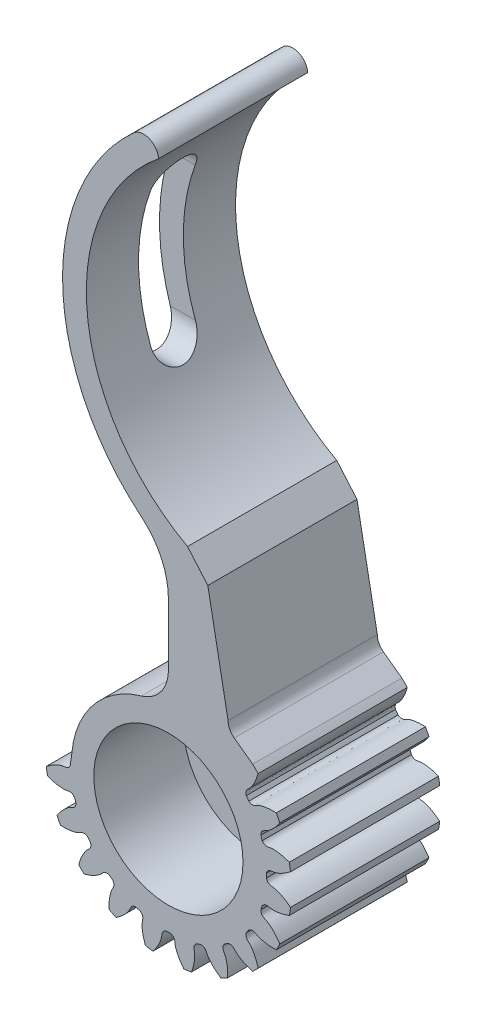
SolidWorks part; units mm, degrees
material "聚脂树脂"
ref_plane "前视基准面" through (0, 0, 0) normal (0, 0, 1) x (1, 0, 0)
ref_plane "上视基准面" through (0, 0, 0) normal (0, 1, 0) x (1, 0, 0)
ref_plane "右视基准面" through (0, 0, 0) normal (1, 0, 0) x (0, 0, -1)
other "Configuration Table"
sketch "草图1" plane through (0, 0, 0) normal (0, 0, 1) x (1, 0, 0)
  circle A0 centre (0, 0) radius 16.5
extrude "凸台-拉伸1" add sketch "草图1" along normal blind 20
ref_axis "基准轴1" through (0, 0, -1.5) along (0, 0, 1)
sketch "草图2" plane through (0, 0, 0) normal (0, 0, 1) x (1, 0, 0)
  line L0 (0, 0) -> (0, 16.5) construction
  circle A0 centre (0, 0) radius 16.5 construction
  arc A1 (0.29, 13.1218) -> (-0.29, 13.1218) centre (0, 0) ccw
  arc A2 (4.7717, 18.7474) -> (-4.7717, 18.7474) centre (0, 0) ccw
  spline S0 degree 3 poles (0.29, 13.1218) (0.9168, 13.3402) (0.8356, 13.7807) (0.9193, 14.205) (0.9283, 14.2463) (0.9395, 14.293) (0.9529, 14.3448) (0.969, 14.4018) (0.9878, 14.4638) (1.0095, 14.5309) (1.0345, 14.6028) (1.0629, 14.6795) (1.0948, 14.7608) (1.1305, 14.8467) (1.1702, 14.9371) (1.2141, 15.0317) (1.2623, 15.1305) (1.315, 15.2334) (1.3725, 15.3401) (1.4349, 15.4506) (1.5023, 15.5646) (1.575, 15.6821) (1.653, 15.8029) (1.7366, 15.9267) (1.826, 16.0534) (1.9211, 16.1829) (2.0223, 16.3149) (2.1296, 16.4493) (2.2432, 16.5859) (2.3632, 16.7244) (2.4897, 16.8646) (2.6229, 17.0065) (2.7628, 17.1496) (2.9095, 17.2939) (3.0632, 17.4391) (3.224, 17.585) (3.3918, 17.7313) (3.567, 17.8779) (3.7493, 18.0245) (3.9391, 18.1709) (4.1363, 18.3167) (4.4122, 18.5125) (4.6259, 18.6545) (4.7717, 18.7474) knots 0 0 0 0 0.165916 0.170906 0.176664 0.183189 0.190482 0.198542 0.207371 0.216967 0.22733 0.238462 0.250361 0.263027 0.276462 0.290664 0.305634 0.321371 0.337876 0.355149 0.37319 0.391998 0.411574 0.431917 0.453028 0.474907 0.497554 0.520968 0.54515 0.570099 0.595817 0.622302 0.649554 0.677575 0.706363 0.735918 0.766242 0.797333 0.829191 0.861818 0.895212 0.929373 1 1 1 1
  spline S1 degree 3 poles (-0.29, 13.1218) (-0.9168, 13.3402) (-0.8356, 13.7807) (-0.9193, 14.205) (-0.9283, 14.2463) (-0.9395, 14.293) (-0.9529, 14.3448) (-0.969, 14.4018) (-0.9878, 14.4638) (-1.0095, 14.5309) (-1.0345, 14.6028) (-1.0629, 14.6795) (-1.0948, 14.7608) (-1.1305, 14.8467) (-1.1702, 14.9371) (-1.2141, 15.0317) (-1.2623, 15.1305) (-1.315, 15.2334) (-1.3725, 15.3401) (-1.4349, 15.4506) (-1.5023, 15.5646) (-1.575, 15.6821) (-1.653, 15.8029) (-1.7366, 15.9267) (-1.826, 16.0534) (-1.9211, 16.1829) (-2.0223, 16.3149) (-2.1296, 16.4493) (-2.2432, 16.5859) (-2.3632, 16.7244) (-2.4897, 16.8646) (-2.6229, 17.0065) (-2.7628, 17.1496) (-2.9095, 17.2939) (-3.0632, 17.4391) (-3.224, 17.585) (-3.3918, 17.7313) (-3.567, 17.8779) (-3.7493, 18.0245) (-3.9391, 18.1709) (-4.1363, 18.3167) (-4.4122, 18.5125) (-4.6259, 18.6545) (-4.7717, 18.7474) knots 0 0 0 0 0.165916 0.170906 0.176664 0.183189 0.190482 0.198542 0.207371 0.216967 0.22733 0.238462 0.250361 0.263027 0.276462 0.290664 0.305634 0.321371 0.337876 0.355149 0.37319 0.391998 0.411574 0.431917 0.453028 0.474907 0.497554 0.520968 0.54515 0.570099 0.595817 0.622302 0.649554 0.677575 0.706363 0.735918 0.766242 0.797333 0.829191 0.861818 0.895212 0.929373 1 1 1 1
extrude "切除-拉伸1" cut sketch "草图2" along normal through all
pattern_circular "阵列(圆周)1" count 20 over 360 about axis through (0, 0, -1.5) along (0, 0, 1) of "切除-拉伸1"
sketch "草图3" plane through (0, 0, 0) normal (0, 0, 1) x (1, 0, 0)
  circle A0 centre (0, 0) radius 15 construction
  dimension "Dn" = 30
sketch "草图4" plane through (0, 0, 0) normal (0, 0, -1) x (-1, 0, 0)
  line L0 (0, 0) -> (67.6919, 0) construction
  line L1 (0, 13.125) -> (0, 76.7697) construction
  line L2 (-15, 0) -> (-15, 67.6903) construction
  line L6 (-7.9502, 14.4584) -> (-11.294, 12.029)
  line L7 (-8, 0) -> (-8, 30.72)
  line L8 (0, 30.72) -> (0, 0)
  line L9 (1.261, 80) -> (1.32, 76)
  line L10 (-8, 0) -> (0, 0)
  circle A2 centre (-15, 55.76) radius 26 construction
  arc A4 (-8, 30.72) -> (1.32, 76) centre (-15, 55.76) ccw
  arc A6 (0.29, 13.1218) -> (-0.29, 13.1218) centre (0, 0) ccw construction
  arc A7 (-2.0665, 16.3701) -> (-3.0932, 16.2075) centre (0, 0) ccw construction
  arc A8 (-3.7791, 12.5692) -> (-4.3306, 12.39) centre (0, 0) ccw construction
  arc A9 (-7.024, 14.9303) -> (-7.9502, 14.4584) centre (0, 0) ccw construction
  arc A10 (0, 13.125) -> (-0.29, 13.1218) centre (0, 0) ccw
  arc A11 (-2.0665, 16.3701) -> (-3.0932, 16.2075) centre (0, 0) ccw
  arc A12 (-3.7791, 12.5692) -> (-4.3306, 12.39) centre (0, 0) ccw
  arc A13 (-7.024, 14.9303) -> (-7.9502, 14.4584) centre (0, 0) ccw
  arc A14 (-7.4782, 10.7862) -> (-7.9474, 10.4453) centre (0, 0) ccw construction
  arc A15 (-7.4782, 10.7862) -> (-7.9474, 10.4453) centre (0, 0) ccw
  circle A16 centre (0, 0) radius 12.5
  circle A17 centre (-15, 55.76) radius 29.189 construction
  arc A18 (0, 30.72) -> (1.261, 80) centre (-15, 55.76) ccw
  spline S2 degree 3 poles (3856.7688, 1071.746) (-40.9447, -7.0022) (0.397, 7.533) (-0.9224, 14.2207) (-0.9359, 14.2793) (-0.9529, 14.3448) (-0.969, 14.4018) (-0.9951, 14.4881) (-1.0357, 14.6084) (-1.0961, 14.7664) (-1.1716, 14.9426) (-1.2638, 15.1361) (-1.3741, 15.3456) (-1.5041, 15.5702) (-1.6549, 15.8084) (-1.7965, 16.0133) (-1.9211, 16.1829) (-22.6396, 43.218) (-204.8238, -56.137) (3987.8439, 293.2807) knots -2.601051 -2.601051 -2.601051 -2.601051 0.165916 0.170906 0.183189 0.190482 0.198542 0.207371 0.22733 0.250361 0.276462 0.305634 0.337876 0.37319 0.411574 0.453028 0.474907 0.497554 14.365332 14.365332 14.365332 14.365332 only from (-0.29, 13.1218) to (-2.0665, 16.3701) construction
  spline S3 degree 3 poles (-3999.1929, -172.5161) (41.1045, 5.9931) (-2.7054, 7.0416) (-3.5171, 13.8097) (-3.5224, 13.8696) (-3.5265, 13.9372) (-3.5289, 13.9963) (-3.5307, 14.0865) (-3.5293, 14.2134) (-3.5206, 14.3824) (-3.5033, 14.5733) (-3.4754, 14.7858) (-3.4352, 15.0192) (-3.381, 15.2729) (-3.3111, 15.5461) (-3.2398, 15.7847) (-3.1737, 15.9845) (8.1764, 48.0988) (212.1463, 9.9046) (-3883.2936, -953.385) knots -2.108482 -2.108482 -2.108482 -2.108482 0.658484 0.663474 0.675757 0.68305 0.691111 0.699939 0.719899 0.742929 0.76903 0.798202 0.830445 0.865758 0.904142 0.945597 0.967475 0.990122 14.8579 14.8579 14.8579 14.8579 only from (-3.7791, 12.5692) to (-3.0932, 16.2075) construction
  spline S4 degree 3 poles (3336.8174, 2211.0982) (-36.7769, -19.3121) (-1.9503, 7.287) (-5.2717, 13.2396) (-5.3027, 13.2912) (-5.3391, 13.3482) (-5.3719, 13.3975) (-5.4235, 13.4715) (-5.4992, 13.5733) (-5.6055, 13.705) (-5.7318, 13.8492) (-5.8792, 14.0047) (-6.0489, 14.1699) (-6.2419, 14.3433) (-6.459, 14.5233) (-6.6569, 14.6744) (-6.8279, 14.7972) (-34.8866, 34.1067) (-177.4517, -116.6835) (3702.0362, 1511.238) knots -2.601051 -2.601051 -2.601051 -2.601051 0.165916 0.170906 0.183189 0.190482 0.198542 0.207371 0.22733 0.250361 0.276462 0.305634 0.337876 0.37319 0.411574 0.453028 0.474907 0.497554 14.365332 14.365332 14.365332 14.365332 only from (-4.3306, 12.39) to (-7.024, 14.9303) construction
  spline S5 degree 3 poles (-0.29, 13.1218) (-0.9168, 13.3402) (-0.8356, 13.7807) (-0.9224, 14.2207) (-0.9359, 14.2793) (-0.9529, 14.3448) (-0.969, 14.4018) (-0.9951, 14.4881) (-1.0357, 14.6084) (-1.0961, 14.7664) (-1.1716, 14.9426) (-1.2638, 15.1361) (-1.3741, 15.3456) (-1.5041, 15.5702) (-1.6549, 15.8084) (-1.828, 16.0589) (-1.969, 16.2466) (-2.0515, 16.3512) (-2.0665, 16.3701) knots 0 0 0 0 0.165916 0.170906 0.183189 0.190482 0.198542 0.207371 0.22733 0.250361 0.276462 0.305634 0.337876 0.37319 0.411574 0.453028 0.497554 0.507432 0.507432 0.507432 0.507432
  spline S6 degree 3 poles (-3.7791, 12.5692) (-3.2504, 12.9706) (-3.4637, 13.3644) (-3.5171, 13.8097) (-3.5224, 13.8696) (-3.5265, 13.9372) (-3.5289, 13.9963) (-3.5307, 14.0865) (-3.5293, 14.2134) (-3.5206, 14.3824) (-3.5033, 14.5733) (-3.4754, 14.7858) (-3.4352, 15.0192) (-3.381, 15.2729) (-3.3111, 15.5461) (-3.224, 15.8378) (-3.1479, 16.0599) (-3.1017, 16.1848) (-3.0932, 16.2075) knots 0.492568 0.492568 0.492568 0.492568 0.658484 0.663474 0.675757 0.68305 0.691111 0.699939 0.719899 0.742929 0.76903 0.798202 0.830445 0.865758 0.904142 0.945597 0.990122 1 1 1 1
  spline S7 degree 3 poles (-4.3306, 12.39) (-4.9943, 12.404) (-5.0532, 12.848) (-5.2717, 13.2396) (-5.3027, 13.2912) (-5.3391, 13.3482) (-5.3719, 13.3975) (-5.4235, 13.4715) (-5.4992, 13.5733) (-5.6055, 13.705) (-5.7318, 13.8492) (-5.8792, 14.0047) (-6.0489, 14.1699) (-6.2419, 14.3433) (-6.459, 14.5233) (-6.701, 14.7081) (-6.8931, 14.843) (-7.0039, 14.9169) (-7.024, 14.9303) knots 0 0 0 0 0.165916 0.170906 0.183189 0.190482 0.198542 0.207371 0.22733 0.250361 0.276462 0.305634 0.337876 0.37319 0.411574 0.453028 0.497554 0.507432 0.507432 0.507432 0.507432
  spline S8 degree 3 poles (-3750.148, -1399.8911) (37.2407, 18.4018) (-4.7489, 5.861) (-7.6124, 12.047) (-7.636, 12.1023) (-7.6607, 12.1653) (-7.6812, 12.2208) (-7.7108, 12.3061) (-7.7487, 12.4272) (-7.7927, 12.5905) (-7.8352, 12.7775) (-7.8743, 12.9882) (-7.9082, 13.2226) (-7.9351, 13.4806) (-7.9531, 13.762) (-7.959, 14.011) (-7.9578, 14.2215) (-7.0871, 48.2713) (198.7024, 74.9766) (-3398.6195, -2106.7268) knots -2.108482 -2.108482 -2.108482 -2.108482 0.658484 0.663474 0.675757 0.68305 0.691111 0.699939 0.719899 0.742929 0.76903 0.798202 0.830445 0.865758 0.904142 0.945597 0.967475 0.990122 14.8579 14.8579 14.8579 14.8579 only from (-7.4782, 10.7862) to (-7.9502, 14.4584) construction
  spline S9 degree 3 poles (2490.235, 3134.0126) (-29.0091, -29.7316) (-4.1066, 6.3277) (-9.105, 10.9626) (-9.1503, 11.0021) (-9.2026, 11.0451) (-9.2491, 11.0817) (-9.321, 11.1362) (-9.4245, 11.2097) (-9.5662, 11.302) (-9.7309, 11.4002) (-9.9192, 11.5025) (-10.1316, 11.6072) (-10.3687, 11.7125) (-10.6308, 11.8165) (-10.8658, 11.8991) (-11.0663, 11.963) (-43.7187, 21.6569) (-132.7094, -165.8082) (3053.8474, 2581.2649) knots -2.601051 -2.601051 -2.601051 -2.601051 0.165916 0.170906 0.183189 0.190482 0.198542 0.207371 0.22733 0.250361 0.276462 0.305634 0.337876 0.37319 0.411574 0.453028 0.474907 0.497554 14.365332 14.365332 14.365332 14.365332 only from (-7.9474, 10.4453) to (-11.294, 12.029) construction
  spline S10 degree 3 poles (-7.4782, 10.7862) (-7.0995, 11.3313) (-7.424, 11.64) (-7.6124, 12.047) (-7.636, 12.1023) (-7.6607, 12.1653) (-7.6812, 12.2208) (-7.7108, 12.3061) (-7.7487, 12.4272) (-7.7927, 12.5905) (-7.8352, 12.7775) (-7.8743, 12.9882) (-7.9082, 13.2226) (-7.9351, 13.4806) (-7.9531, 13.762) (-7.9603, 14.0664) (-7.9566, 14.3011) (-7.9513, 14.4342) (-7.9502, 14.4584) knots 0.492568 0.492568 0.492568 0.492568 0.658484 0.663474 0.675757 0.68305 0.691111 0.699939 0.719899 0.742929 0.76903 0.798202 0.830445 0.865758 0.904142 0.945597 0.990122 1 1 1 1
  spline S11 degree 3 poles (-7.9474, 10.4453) (-8.5829, 10.2536) (-8.7761, 10.6576) (-9.105, 10.9626) (-9.1503, 11.0021) (-9.2026, 11.0451) (-9.2491, 11.0817) (-9.321, 11.1362) (-9.4245, 11.2097) (-9.5662, 11.302) (-9.7309, 11.4002) (-9.9192, 11.5025) (-10.1316, 11.6072) (-10.3687, 11.7125) (-10.6308, 11.8165) (-10.9181, 11.9175) (-11.1425, 11.9864) (-11.2707, 12.0225) (-11.294, 12.029) knots 0 0 0 0 0.165916 0.170906 0.183189 0.190482 0.198542 0.207371 0.22733 0.250361 0.276462 0.305634 0.337876 0.37319 0.411574 0.453028 0.497554 0.507432 0.507432 0.507432 0.507432
  dimension "D4" = 52
  dimension "D5" = 80
  dimension "D3" = 25
  dimension "D1" = 15
  dimension "D2" = 30.72
  dimension "D6" = 76
  dimension "D8" = 8
  dimension "D9" = 30.72
extrude "凸台-拉伸2" add sketch "草图4" against normal blind 20 contours S7 A12 S6 A11 S5 A10 L8 A18 L9 A4 L7 L6 A13 | S11 L7 L6 | L6 S11 A15 S10 region at (7.2884, 22.5711, 0) region at (9.051, 12.2758, 0)
fillet "圆角1" radius 10 1 edges at (0, 30.72, 10)
fillet "圆角2" radius 2 2 edges at (8, 14.4222, 10) (-1.261, 80, 10)
sketch "草图5" plane through (0, 0, 0) normal (0, 0, -1) x (-1, 0, 0)
  line L0 (0, 0) -> (47.9973, 0) construction
  line L1 (0, 0) -> (0, 54.3289) construction
sketch "草图7" plane through (0, 0, 20) normal (0, 0, 1) x (1, 0, 0)
  line L0 (0, 0) -> (42.9933, 0) construction
  line L1 (0, 0) -> (0, 51.6895) construction
  circle A0 centre (0, 0) radius 10
  dimension "D1" = 20
extrude "切除-拉伸2" cut sketch "草图7" against normal blind 12
sketch "草图8" plane through (0, 0, 8) normal (0, 0, 1) x (1, 0, 0)
  line L0 (0, 0) -> (25.4464, 0) construction
  line L1 (0, 0) -> (0, 31.9913) construction
  circle A0 centre (0, 0) radius 3.5
  circle A1 centre (0, 7) radius 1.5
  circle A2 centre (7, 0) radius 1.5
  circle A3 centre (0, -7) radius 1.5
  circle A4 centre (-7, 0) radius 1.5
  dimension "D1" = 3
  dimension "D2" = 7
  dimension "D4" = 3
  dimension "D3" = 7
  dimension "D5" = 7
extrude "切除-拉伸3" cut sketch "草图8" against normal blind 10
chamfer "倒角1" distance 5 angle 45 1 edges at (8, 30.72, 10) first distance on face at (8, 23.0806, 10)
sketch "草图10" plane through (0, 0, 0) normal (0, 0, -1) x (-1, 0, 0)
  circle A0 centre (0, 0) radius 10
  circle A1 centre (-7, 0) radius 1.5 construction
  circle A2 centre (0, -7) radius 1.5 construction
  circle A3 centre (0, 0) radius 3.5 construction
  circle A4 centre (7, 0) radius 1.5 construction
  circle A5 centre (0, 7) radius 1.5 construction
  circle A6 centre (-7, 0) radius 1.5
  circle A7 centre (0, -7) radius 1.5
  circle A8 centre (0, 0) radius 3.5
  circle A9 centre (7, 0) radius 1.5
  circle A10 centre (0, 7) radius 1.5
  dimension "D1" = 20
extrude "凸台-拉伸3" add sketch "草图10" along normal blind 2
fillet "圆角3" radius 2 1 edges at (10, 0, 0)
sketch "草图11" plane through (0, 0, 0) normal (1, 0, 0) x (0, 0, -1)
  line L0 (-10, 46.72) -> (-10, 64.72) construction
  line L1 (-13, 46.72) -> (-13, 64.72)
  line L2 (-7, 46.72) -> (-7, 64.72)
  line L3 (0, 32.9259) -> (0, 76) construction
  arc A0 (-13, 46.72) -> (-7, 46.72) centre (-10, 46.72) ccw
  arc A1 (-7, 64.72) -> (-13, 64.72) centre (-10, 64.72) ccw
  point P2 (-10, 55.72)
  dimension "D2" = 3
  dimension "D1" = 18
  dimension "D3" = 10
  dimension "D4" = 55.72
extrude "切除-拉伸4" cut sketch "草图11" against normal blind 24
sketch "草图12" plane through (0, 0, -2) normal (0, 0, -1) x (-1, 0, 0)
  line L0 (0, 0) -> (0, 22.0387)
  line L1 (0, 0) -> (32.0939, 0)
  line L2 (0, 22.0387) -> (32.0939, 22.0387)
  line L3 (32.0939, 22.0387) -> (32.0939, 0)
  line L4 (-5.283, 29.7615) -> (-8, 15.4412)
  line L5 (-2.566, 32.9259) -> (-8, 26.5971) construction
  line L6 (-8, 15.4412) -> (-8, 26.5971)
  line L7 (-8, 26.5971) -> (-5.283, 29.7615)
  circle A0 centre (0, 0) radius 13
  dimension "D1" = 26
extrude "切除-拉伸5" cut sketch "草图12" against normal blind 26 contours A0 L1 L3 L2 L0 | L7 L6 L4 region at (-18.4794, 12.2903, -2) region at (7.0943, 23.9333, -2)
fillet "圆角4" radius 10 1 edges at (-13, 0, 10)
fillet "圆角5" radius 5 1 edges at (0, 13, 10)
